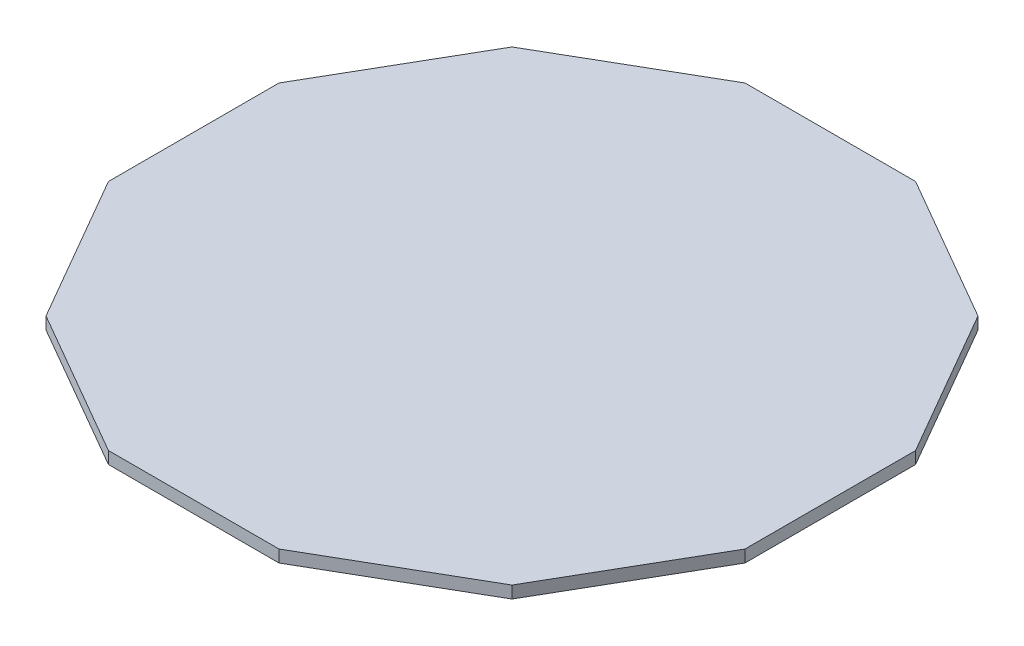
SolidWorks part; units mm, degrees
material "ABS PC"
ref_plane "Front Plane" through (0, 0, 0) normal (0, 0, 1) x (1, 0, 0)
ref_plane "Top Plane" through (0, 0, 0) normal (0, 1, 0) x (1, 0, 0)
ref_plane "Right Plane" through (0, 0, 0) normal (1, 0, 0) x (0, 0, -1)
sketch "Sketch1" plane through (0, 0, 0) normal (0, 1, 0) x (1, 0, 0)
  line L0 (19.722, 73.6035) -> (-19.722, 73.6035)
  line L1 (-19.722, 73.6035) -> (-53.8815, 53.8815)
  line L2 (-53.8815, 53.8815) -> (-73.6035, 19.722)
  line L3 (-73.6035, 19.722) -> (-73.6035, -19.722)
  line L4 (-73.6035, -19.722) -> (-53.8815, -53.8815)
  line L5 (-53.8815, -53.8815) -> (-19.722, -73.6035)
  line L6 (-19.722, -73.6035) -> (19.722, -73.6035)
  line L7 (19.722, -73.6035) -> (53.8815, -53.8815)
  line L8 (53.8815, -53.8815) -> (73.6035, -19.722)
  line L9 (73.6035, -19.722) -> (73.6035, 19.722)
  line L10 (73.6035, 19.722) -> (53.8815, 53.8815)
  line L11 (53.8815, 53.8815) -> (19.722, 73.6035)
  circle A0 centre (0, 0) radius 76.2
  dimension "D1" = 152.4
extrude "Boss-Extrude1" add sketch "Sketch1" against normal blind 2.921 contours L10 L11 L0 L1 L2 L3 L4 L5 L6 L7 L8 L9 region at (0, 0, 0)
sketch "Sketch2" plane through (0, 0, 0) normal (0, 1, 0) x (1, 0, 0)
  line L24 (76.5245, 20.5047) -> (56.0199, 56.0199)
  line L25 (56.0199, 56.0199) -> (20.5047, 76.5245)
  line L26 (20.5047, 76.5245) -> (-20.5047, 76.5245)
  line L27 (-20.5047, 76.5245) -> (-56.0199, 56.0199)
  line L28 (-56.0199, 56.0199) -> (-76.5245, 20.5047)
  line L29 (-76.5245, 20.5047) -> (-76.5245, -20.5047)
  line L30 (-76.5245, -20.5047) -> (-56.0199, -56.0199)
  line L31 (-56.0199, -56.0199) -> (-20.5047, -76.5245)
  line L32 (-20.5047, -76.5245) -> (20.5047, -76.5245)
  line L33 (20.5047, -76.5245) -> (56.0199, -56.0199)
  line L34 (56.0199, -56.0199) -> (76.5245, -20.5047)
  line L35 (76.5245, -20.5047) -> (76.5245, 20.5047)
  line L36 (76.5245, 20.5047) -> (56.0199, 56.0199)
  line L37 (56.0199, 56.0199) -> (20.5047, 76.5245)
  line L38 (20.5047, 76.5245) -> (-20.5047, 76.5245)
  line L39 (-20.5047, 76.5245) -> (-56.0199, 56.0199)
  line L40 (-56.0199, 56.0199) -> (-76.5245, 20.5047)
  line L41 (-76.5245, 20.5047) -> (-76.5245, -20.5047)
  line L42 (-76.5245, -20.5047) -> (-56.0199, -56.0199)
  line L43 (-56.0199, -56.0199) -> (-20.5047, -76.5245)
  line L44 (-20.5047, -76.5245) -> (20.5047, -76.5245)
  line L45 (20.5047, -76.5245) -> (56.0199, -56.0199)
  line L46 (56.0199, -56.0199) -> (76.5245, -20.5047)
  line L47 (76.5245, -20.5047) -> (76.5245, 20.5047)
  line L60 (73.6035, 19.722) -> (53.8815, 53.8815)
  line L61 (53.8815, 53.8815) -> (19.722, 73.6035)
  line L62 (19.722, 73.6035) -> (-19.722, 73.6035)
  line L63 (-19.722, 73.6035) -> (-53.8815, 53.8815)
  line L64 (-53.8815, 53.8815) -> (-73.6035, 19.722)
  line L65 (-73.6035, 19.722) -> (-73.6035, -19.722)
  line L66 (-73.6035, -19.722) -> (-53.8815, -53.8815)
  line L67 (-53.8815, -53.8815) -> (-19.722, -73.6035)
  line L68 (-19.722, -73.6035) -> (19.722, -73.6035)
  line L69 (19.722, -73.6035) -> (53.8815, -53.8815)
  line L70 (53.8815, -53.8815) -> (73.6035, -19.722)
  line L71 (73.6035, -19.722) -> (73.6035, 19.722)
  line L72 (73.6035, 19.722) -> (53.8815, 53.8815)
  line L73 (53.8815, 53.8815) -> (19.722, 73.6035)
  line L74 (19.722, 73.6035) -> (-19.722, 73.6035)
  line L75 (-19.722, 73.6035) -> (-53.8815, 53.8815)
  line L76 (-53.8815, 53.8815) -> (-73.6035, 19.722)
  line L77 (-73.6035, 19.722) -> (-73.6035, -19.722)
  line L78 (-73.6035, -19.722) -> (-53.8815, -53.8815)
  line L79 (-53.8815, -53.8815) -> (-19.722, -73.6035)
  line L80 (-19.722, -73.6035) -> (19.722, -73.6035)
  line L81 (19.722, -73.6035) -> (53.8815, -53.8815)
  line L82 (53.8815, -53.8815) -> (73.6035, -19.722)
  line L83 (73.6035, -19.722) -> (73.6035, 19.722)
  dimension "D1" = 2.921
  dimension "D2" = 0
extrude "Boss-Extrude2" add sketch "Sketch2" against normal up to surface (2.921 mm away) up to face at (0, -2.921, 0)
